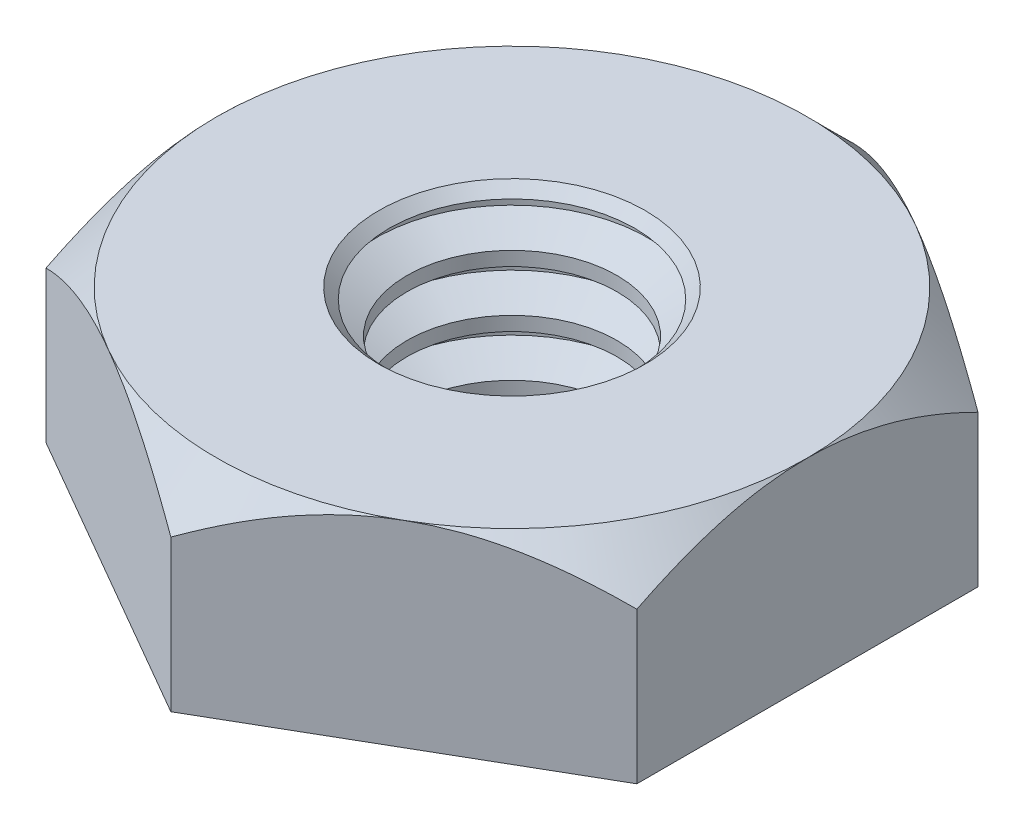
SolidWorks part; units mm, degrees
ref_plane "Front" through (0, 0, 0) normal (0, 0, 1) x (1, 0, 0)
ref_plane "Top" through (0, 0, 0) normal (0, 1, 0) x (1, 0, 0)
ref_plane "Right" through (0, 0, 0) normal (1, 0, 0) x (0, 0, -1)
sketch "Sketch1" plane through (0, 0, 0) normal (0, 1, 0) x (1, 0, 0)
  line L1 (0, 2.7496) -> (-2.3812, 1.3748)
  line L2 (-2.3812, 1.3748) -> (-2.3812, -1.3748)
  line L3 (-2.3812, -1.3748) -> (0, -2.7496)
  line L4 (0, -2.7496) -> (2.3812, -1.3748)
  line L5 (2.3812, -1.3748) -> (2.3813, 1.3748)
  line L6 (2.3813, 1.3748) -> (0, 2.7496)
  circle A0 centre (0, 0) radius 2.3812 construction
  dimension "Hex Flats" = 4.7625
extrude "Extrude1" add sketch "Sketch1" along normal blind 1.5875
sketch "Sketch3" plane through (0, 0, 0) normal (1, 0, 0) x (0, 0, -1)
  line L0 (2.3812, 1.5875) -> (2.7496, 1.2191)
  line L1 (1.3748, 1.5875) -> (2.7496, 1.5875) construction
  line L2 (2.7496, 1.5875) -> (2.7496, 0) construction
  line L3 (2.7496, 1.2191) -> (2.7496, 1.5875)
  line L4 (2.7496, 1.5875) -> (2.3812, 1.5875)
  line L5 (0, 0.542) -> (0, -0.542) construction
  dimension "D1" = 45
  dimension "D2" = 4.7625
revolve "Cut-Revolve2" cut sketch "Sketch3" angle 360 about L5
sketch "Sketch2" plane through (0, 0, 0) normal (0, 0, 1) x (1, 0, 0)
  line L0 (0, 1.6636) -> (0, -0.3796) construction
  line L1 (0, 1.5875) -> (0.8467, 1.5875)
  line L3 (0, 1.5875) -> (2.3812, 1.5875) construction
  line L4 (0, 1.1339) -> (0.8467, 1.1339)
  line L5 (0.8467, 1.5875) -> (1.0922, 1.4458)
  line L6 (1.0922, 1.4458) -> (1.0922, 1.3891)
  line L7 (1.0922, 1.3891) -> (0.8467, 1.2473)
  line L9 (0.8467, 1.1339) -> (0.8467, 1.2473)
  line L10 (0, 1.1339) -> (0, 1.5875)
  line L11 (0.8467, 1.5875) -> (0.8467, 1.2473) construction
  line L12 (1.0922, 1.4174) -> (0.8467, 1.4174) construction
  dimension "D1" = 60
  dimension "D2" = 0.1134
  dimension "D5" = 0.0567
  dimension "Pitch" = 0.4536
  dimension "Major Dia." = 2.1844
revolve "Cut-Revolve1" cut sketch "Sketch2" angle 360 about L0
pattern_linear "LPattern2" count 4 spacing 0.4536 along (0, -1, 0) of "Cut-Revolve1"
chamfer "Chamfer1" distance 0.2268 angle 45 1 edges at (0, 1.5875, 0.8467) first distance on face at (0, 1.5875, 0)
ref_axis "Axis1" through (0, 1.9085, 0) along (0, -1, 0)
equation "\"D5@Sketch2\"=\"Pitch@Sketch2\"/8"
equation "\"D2@Sketch2\"=\"Pitch@Sketch2\"/4"
equation "\"D3@LPattern2\"=\"Pitch@Sketch2\""
equation "\"D1@LPattern2\"=int(\"Height@Extrude1\"/\"Pitch@Sketch2\")+1"
equation "\"D2@Sketch3\"=\"Hex Flats@Sketch1\""
equation "\"D1@Chamfer1\"=\"Pitch@Sketch2\"/2"
